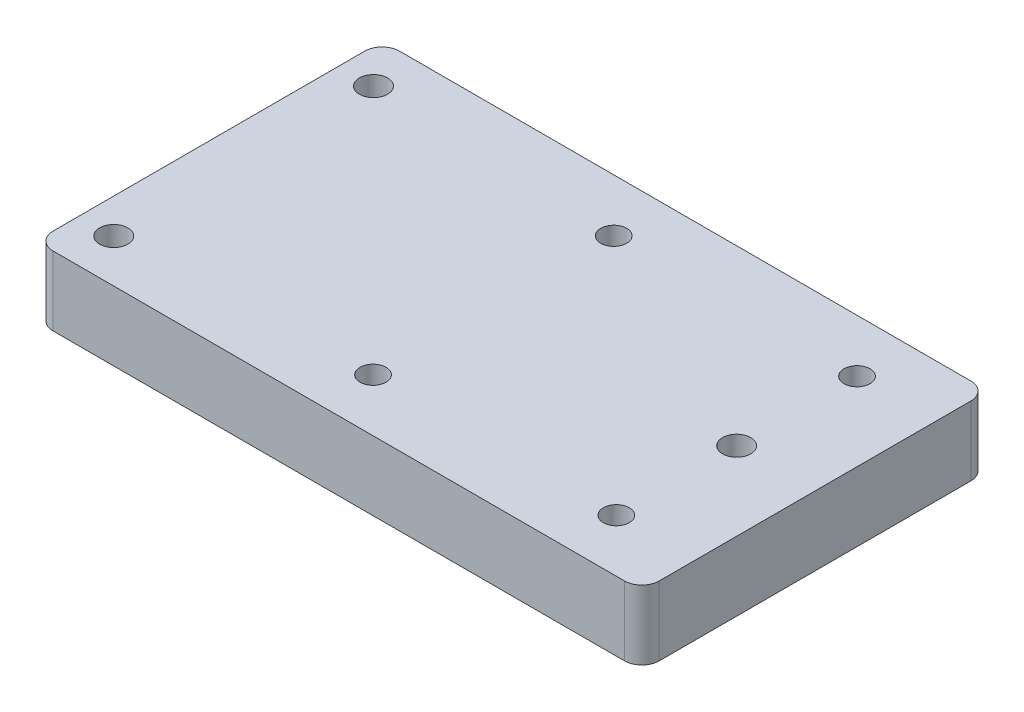
SolidWorks part; units mm, degrees
ref_plane "Front Plane" through (0, 0, 0) normal (0, 0, 1) x (1, 0, 0)
ref_plane "Top Plane" through (0, 0, 0) normal (0, 1, 0) x (1, 0, 0)
ref_plane "Right Plane" through (0, 0, 0) normal (1, 0, 0) x (0, 0, -1)
sketch "Sketch1" plane through (0, 0, 0) normal (0, 1, 0) x (1, 0, 0)
  line L1 (-35, 20) -> (35, 20)
  line L2 (-35, 20) -> (-35, -20)
  line L3 (-35, -20) -> (35, -20)
  line L4 (35, 20) -> (35, -20)
  line L5 (-35, 20) -> (35, -20) construction
  line L6 (-35, -20) -> (35, 20) construction
  point P0 (0, 0)
  dimension "D1" = 70
  dimension "D2" = 40
extrude "Boss-Extrude1" add sketch "Sketch1" along normal blind 8
hole_wizard "Ø3.0mm Dowel Hole1" positions "Sketch2" profile "Sketch3" hole size "Ø3.0" standard "ANSI Metric" end condition through all
sketch "Sketch2" plane through (0, 8, 0) normal (0, 1, 0) x (1, 0, 0)
  line L2 (35, -20) -> (35, 20) construction
  line L3 (-35, -20) -> (35, -20) construction
  point P0 (-2.15, 13.9)
  point P2 (25.95, 13.9)
  point P4 (-2.15, -13.9)
  point P6 (25.95, -13.9)
  dimension "D3" = 27.8
  dimension "D1" = 37.15
  dimension "D2" = 9.05
  dimension "D4" = 6.1
sketch "Sketch3" plane through (-2.15, 8, -13.9) normal (1, 0, 0) x (0, 0, 1)
  line L0 (0, 0) -> (0, 8)
  line L1 (0, 8) -> (1.5, 8)
  line L2 (1.5, 8) -> (1.5, 0)
  line L5 (1.5, 0) -> (0, 0)
  line L11 (0, -6.35) -> (0, 107.95) construction
  dimension "Thru Hole Dia." = 3
  dimension "Thru Hole Depth" = 8
hole_wizard "#4 Clearance Hole1" positions "Sketch4" profile "Sketch5" hole size "#4" standard "ANSI Inch" end condition through all
sketch "Sketch4" plane through (0, 8, 0) normal (0, 1, 0) x (1, 0, 0)
  line L0 (-35, 20) -> (-35, -20) construction
  line L1 (-35, -20) -> (35, -20) construction
  line L2 (35, 20) -> (-35, 20) construction
  line L3 (35, -20) -> (35, 20) construction
  point P0 (-31, 15)
  point P2 (-31, -15)
  point P11 (25.95, 0)
  dimension "D1" = 4
  dimension "D2" = 4
  dimension "D3" = 5
  dimension "D4" = 5
  dimension "D5" = 9.05
sketch "Sketch5" plane through (-31, 8, -15) normal (1, 0, 0) x (0, 0, 1)
  line L0 (0, 0) -> (0, 8)
  line L1 (0, 8) -> (1.6319, 8)
  line L2 (1.6319, 8) -> (1.6319, 0)
  line L5 (1.6319, 0) -> (0, 0)
  line L11 (0, -6.35) -> (0, 107.95) construction
  dimension "Thru Hole Dia." = 3.2639
  dimension "Thru Hole Depth" = 8
fillet "Fillet1" radius 2 4 edges at (-35, 4, -20) (-35, 4, 20) (35, 4, -20) (35, 4, 20)
equation "\"D4@Sketch2\"=(40-\"D3@Sketch2\")/2"
equation "\"D4@Sketch4\"=\"D3@Sketch4\""
equation "\"D2@Sketch4\"=\"D1@Sketch4\""
